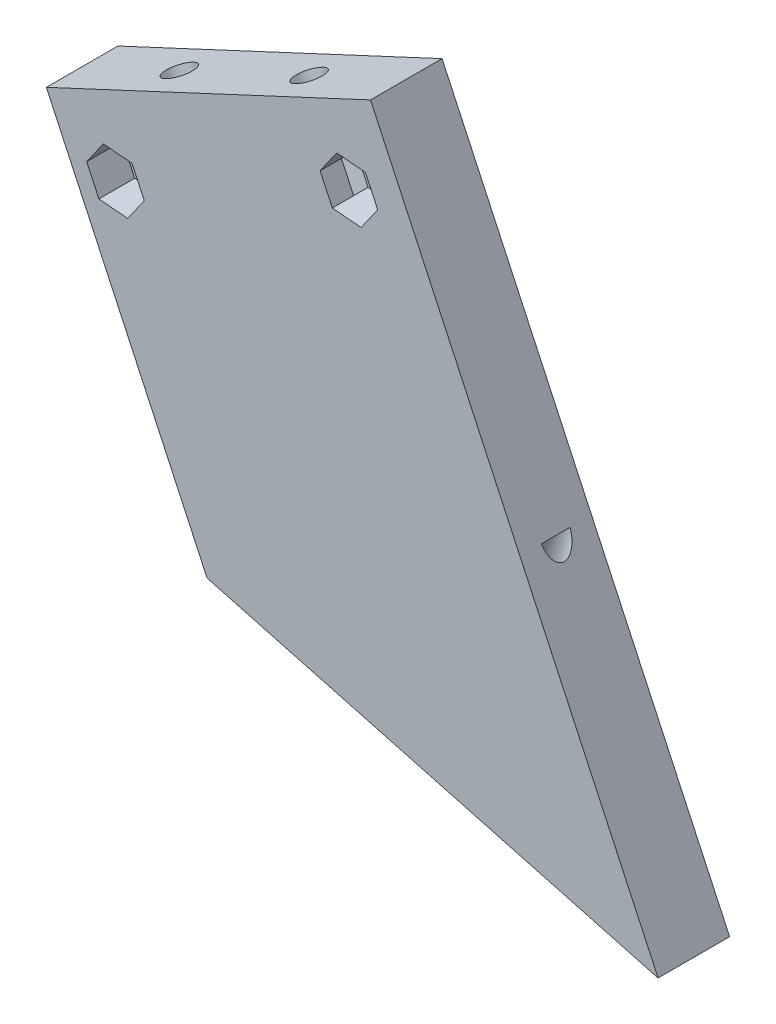
SolidWorks part; units mm, degrees
material "ABS"
ref_plane "Front Plane" through (0, 0, 0) normal (0, 0, 1) x (1, 0, 0)
ref_plane "Top Plane" through (0, 0, 0) normal (0, 1, 0) x (1, 0, 0)
ref_plane "Right Plane" through (0, 0, 0) normal (1, 0, 0) x (0, 0, -1)
sketch "Sketch1" plane through (0, 0, 0) normal (0, 0, 1) x (1, 0, 0)
  line L0 (127.3464, -36.4832) -> (87.1479, 49.7228)
  line L1 (198.5484, -55.5617) -> (5.3632, -3.7979) construction
  line L2 (87.1479, 49.7228) -> (41.8325, 28.5919)
  line L3 (41.8325, 28.5919) -> (64.3001, -19.59)
  line L4 (64.3001, -19.59) -> (127.3464, -36.4832)
  line L6 (189.2372, 97.3278) -> (-129.7831, -51.4338) construction
  line L7 (127.3464, -36.4832) -> (87.1479, 49.7228) construction
  dimension "D1" = 50
extrude "Boss-Extrude1" add sketch "Sketch1" against normal blind 10
sketch "Sketch2" plane through (-3.4798, 7.4624, 0) normal (-0.4226, 0.9063, 0) x (0.9063, 0.4226, 0)
  line L0 (49.9966, 5) -> (99.9966, 5) construction
  line L1 (49.9966, 10) -> (49.9966, 0) construction
  line L2 (99.9966, 10) -> (99.9966, 0) construction
  line L3 (74.9966, 10) -> (74.9966, 0) construction
  line L4 (84.9966, 0.9585) -> (88.4966, 2.9793)
  line L5 (88.4966, 2.9793) -> (88.4966, 7.0207)
  line L6 (88.4966, 7.0207) -> (84.9966, 9.0415)
  line L7 (84.9966, 9.0415) -> (81.4966, 7.0207)
  line L8 (81.4966, 7.0207) -> (81.4966, 2.9793)
  line L9 (81.4966, 2.9793) -> (84.9966, 0.9585)
  line L10 (99.9966, 10) -> (49.9966, 10) construction
  line L11 (99.9966, 0) -> (49.9966, 0) construction
  line L12 (68.4966, 2.9793) -> (64.9966, 0.9585)
  line L13 (64.9966, 0.9585) -> (61.4966, 2.9793)
  line L14 (68.4966, 7.0207) -> (68.4966, 2.9793)
  line L15 (64.9966, 9.0415) -> (68.4966, 7.0207)
  line L16 (61.4966, 7.0207) -> (64.9966, 9.0415)
  line L17 (61.4966, 2.9793) -> (61.4966, 7.0207)
  circle A0 centre (84.9966, 5) radius 3.5 construction
  circle A1 centre (84.9966, 5) radius 2
  circle A2 centre (64.9966, 5) radius 3.5 construction
  circle A3 centre (64.9966, 5) radius 2
  dimension "D3" = 4
  dimension "D1" = 15
  dimension "D2" = 7
extrude "Cut-Extrude1" cut sketch "Sketch2" against normal through all contours A3 | A1 region at (73.5533, 43.3835, -5) region at (55.4272, 34.9312, -5)
extrude "Cut-Extrude2" cut sketch "Sketch2<3>" against normal through all from offset 4 offset against normal yes
sketch "Sketch2<3>" plane through (-3.4798, 7.4624, 0) normal (-0.4226, 0.9063, 0) x (0.9063, 0.4226, 0) same geometry as "Sketch2"
sketch "Sketch3" plane through (-0.5902, -2.2027, 0) normal (-0.2588, -0.9659, 0) x (0.9659, -0.2588, 0)
  line L0 (132.4498, -5) -> (67.1794, -5) construction
  line L1 (132.4498, -10) -> (132.4498, 0) construction
  line L2 (67.1794, -10) -> (67.1794, 0) construction
  circle A0 centre (82.8091, -5) radius 2
  circle A1 centre (102.8936, -5) radius 2
  circle A2 centre (102.8936, -5) radius 1.5 construction
  circle A3 centre (82.8091, -5) radius 1.5 construction
  dimension "D1" = 4
  dimension "D2" = 4
extrude "Cut-Extrude3" cut sketch "Sketch3" against normal blind 35
sketch "Sketch4" plane through (0, 0, 0) normal (0, 0, 1) x (1, 0, 0)
  line L0 (127.3464, -36.4832) -> (87.1479, 49.7228) construction
  line L1 (88.1497, 36.9265) -> (86.4417, 40.5893)
  line L2 (86.4417, 40.5893) -> (82.4157, 40.9416)
  line L3 (82.4157, 40.9416) -> (80.0976, 37.631)
  line L4 (80.0976, 37.631) -> (81.8056, 33.9682)
  line L5 (81.8056, 33.9682) -> (85.8317, 33.616)
  line L6 (85.8317, 33.616) -> (88.1497, 36.9265)
  line L7 (87.1479, 49.7228) -> (41.8325, 28.5919) construction
  line L8 (55.5227, 21.7123) -> (53.8147, 25.3751)
  line L9 (53.8147, 25.3751) -> (49.7886, 25.7273)
  line L10 (49.7886, 25.7273) -> (47.4705, 22.4167)
  line L11 (47.4705, 22.4167) -> (49.1785, 18.7539)
  line L12 (49.1785, 18.7539) -> (53.2046, 18.4017)
  line L13 (53.2046, 18.4017) -> (55.5227, 21.7123)
  line L14 (87.1479, 49.7228) -> (41.8325, 28.5919) construction
  line L15 (41.8325, 28.5919) -> (64.3001, -19.59) construction
  circle A0 centre (84.1237, 37.2788) radius 2
  circle A1 centre (84.1237, 37.2788) radius 3.5 construction
  circle A2 centre (51.4966, 22.0645) radius 2
  circle A3 centre (51.4966, 22.0645) radius 3.5 construction
  dimension "D4" = 4
  dimension "D7" = 4
  dimension "D1" = 8
  dimension "D2" = 10
  dimension "D3" = 7
  dimension "D5" = 0
  dimension "D6" = 7
  dimension "D8" = 10
  dimension "D9" = 6
extrude "Cut-Extrude4" cut sketch "Sketch4" against normal blind 10 contours A0 | A2 region at (84.1237, 37.2788, 0) region at (51.4966, 22.0645, 0)
extrude "Cut-Extrude5" cut sketch "Sketch4<3>" against normal blind 5 from surface starting at face at (86.1237, 37.2788, 0)
sketch "Sketch4<3>" plane through (0, 0, 0) normal (0, 0, 1) x (1, 0, 0) same geometry as "Sketch4"
